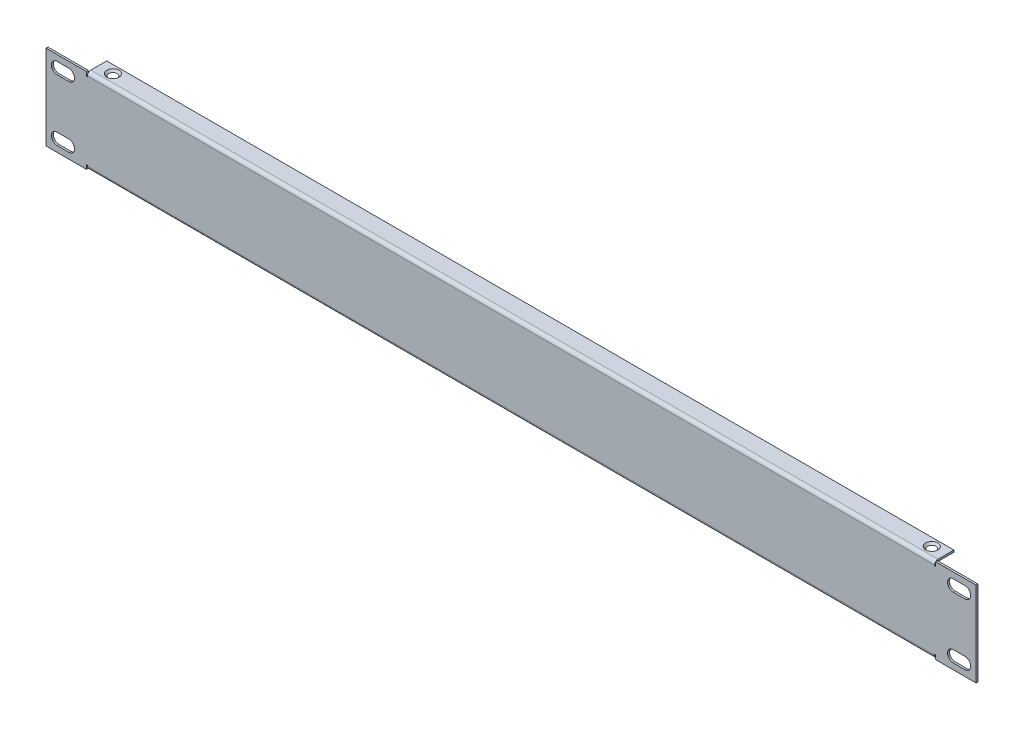
SolidWorks part; units mm, degrees
note: The reader was unsure of these and kept them because the rebuilt part matched: flange length of "Edge-Flange-Mouning".
ref_plane "Front Plane" through (0, 0, 0) normal (0, 0, 1) x (1, 0, 0)
ref_plane "Top Plane" through (0, 0, 0) normal (0, 1, 0) x (1, 0, 0)
ref_plane "Right Plane" through (0, 0, 0) normal (1, 0, 0) x (0, 0, -1)
sketch "Sketch1" plane through (0, 0, 0) normal (0, 0, 1) x (1, 0, 0)
  line L1 (0, 0) -> (-241.3, 0)
  line L2 (0, 0) -> (0, 22)
  line L3 (0, 22) -> (-241.3, 22)
  line L4 (-241.3, 0) -> (-241.3, 22)
  dimension "D1" = 22
  dimension "D2" = 241.3
sheet metal parameters "Sheet-Metal" thickness 1 parameters "D1"=0.7366
base flange "Base-Flange" sketch "Sketch1" thickness 1 reverse thickness direction no parameters "D1"=0.7366
edge flange "Edge-Flange-Mouning" sketch "Sketch12" flange angle 90 flange length 10 flange position material inside bend radius 0.7366 thickness 1 parameters "D6"=10
sketch "Sketch12" plane through (0, 22, -1) normal (0, 1, 0) x (1, 0, 0)
  line L0 (0, 0) -> (-241.3, 0) construction
  line L1 (0, 0) -> (-219.8, 0)
  line L2 (-219.8, 0) -> (-219.8, 9)
  line L3 (-219.8, 9) -> (0, 9)
  line L4 (0, 9) -> (0, 0)
  line L6 (-241.3, 0) -> (-241.3, -1) construction
  dimension "D1" = 21.5
bend "EdgeBend1" bend radius 0.7366 bend angle 90 parameters "D5"=1
sketch "Sketch13" plane through (0, 0, 0) normal (0, 0, 1) x (1, 0, 0)
  line L0 (-241.3, 0) -> (0, 0) construction
  line L2 (0, 0) -> (0, 20.2634) construction
  line L5 (-229.5, 15.9) -> (-235.5, 15.9) construction
  line L6 (-229.5, 12.9) -> (-235.5, 12.9)
  line L7 (-229.5, 18.9) -> (-235.5, 18.9)
  arc A2 (-229.5, 12.9) -> (-229.5, 18.9) centre (-229.5, 15.9) ccw
  arc A3 (-235.5, 18.9) -> (-235.5, 12.9) centre (-235.5, 15.9) ccw
  point P0 (-232.5, 15.9)
  point P13 (-232.5, 15.9)
  dimension "D3" = 232.5
  dimension "D1" = 15.9
extrude "Cut-Extrude-Mounting" cut sketch "Sketch13" against normal blind 1
mirror "Mirror-Vertical" about plane through (0, 0, -1) normal (1, 0, 0) of bodies 103 104
mirror "Mirror-Horizontal"
bend "MirrorBend1" bend radius 0.7366 bend angle 90 parameters "D5"=2
hole_wizard "CSK for M3 Countersunk Flat Head Screw5" positions "Sketch14" profile "Sketch15" countersink size "M3" standard "ISO" end condition through all
sketch "Sketch14" plane through (0, 22, 0) normal (0, 1, 0) x (1, 0, 0)
  line L3 (-219.0634, 10) -> (-205.8, 10) construction
  line L8 (0, 0) -> (0, 10) construction
  point P20 (-212.4317, 5.8683)
  point P30 (212.4317, 5.8683)
sketch "Sketch15" plane through (-212.4317, 22, -5.8683) normal (1, 0, 0) x (0, 0, 1)
  line L0 (0, 0) -> (0, 44)
  line L1 (0, 44) -> (1.6, 44)
  line L2 (1.6, 44) -> (1.6, 1.55)
  line L3 (1.6, 1.55) -> (3.15, 0)
  line L5 (3.15, 0) -> (0, 0)
  line L6 (-1.6, 1.55) -> (-3.15, 0) construction
  line L11 (0, -6.35) -> (0, 107.95) construction
  dimension "Thru Hole Dia." = 3.2
  dimension "Thru Hole Depth" = 44
  dimension "Near C'Sink Dia." = 6.3
  dimension "Near C'Sink Angle" = 90
hole_wizard "CSK for M3 Countersunk Flat Head Screw6" positions "Sketch16" profile "Sketch17" countersink size "M3" standard "ISO" end condition through all
sketch "Sketch16" plane through (0, -22, 0) normal (0, -1, 0) x (-1, 0, 0)
  point P3 (-212.4317, 5.8683)
  point P5 (212.4317, 5.8683)
sketch "Sketch17" plane through (212.4317, -22, -5.8683) normal (1, 0, 0) x (0, 0, -1)
  line L0 (0, 0) -> (0, 44)
  line L1 (0, 44) -> (1.6, 44)
  line L2 (1.6, 44) -> (1.6, 1.55)
  line L3 (1.6, 1.55) -> (3.15, 0)
  line L4 (3.15, 0) -> (0, 0)
  line L5 (-1.6, 1.55) -> (-3.15, 0) construction
  line L6 (0, -6.35) -> (0, 107.95) construction
  dimension "Thru Hole Dia." = 3.2
  dimension "Thru Hole Depth" = 44
  dimension "Near C'Sink Dia." = 6.3
  dimension "Near C'Sink Angle" = 90
flat pattern "Flat-Pattern1" [suppressed]
sketch "Bend-Lines1" plane through (0, 0, 0) normal (0, 0, 1) x (1, 0, 0)
  line L0 (-219.8, -20.3237) -> (219.8, -20.3237) construction
  line L1 (219.8, 20.3237) -> (-219.8, 20.3237) construction
  line L2 (-219.8, -20.3237) -> (219.8, -20.3237) construction
  line L3 (219.8, 20.3237) -> (-219.8, 20.3237) construction
sketch3d "Bounding-Box1" [suppressed]
  line L0 (-241.3, -28.6473, 0) -> (241.3, -28.6473, 0) construction
  line L1 (-241.3, 28.6473, 0) -> (241.3, 28.6473, 0) construction
  line L2 (-241.3, -28.6473, 0) -> (-241.3, 28.6473, 0) construction
  line L3 (241.3, -28.6473, 0) -> (241.3, 28.6473, 0) construction
bend of the flat pattern "Flatten-<EdgeBend1>1"
bend of the flat pattern "Flatten-<MirrorBend1>1"
equation "\"RackUnitHeight\"= 44"
equation "\"RackUnitWidth\"= 482.6"
equation "\"RackUnitInnerWidth\"= 440"
equation "\"RackUnitMountingHoleHorizontalSpacing\"= 465"
equation "\"RackUnitMountingHoleVerticalSpacing\"= 15.9"
equation "\"D1@Sketch1\" = \"RackUnitHeight@Rack unit<1>.Assembly\" / 2"
equation "\"D2@Sketch1\" = \"RackUnitWidth@Rack unit<1>.Assembly\" / 2"
equation "\"D1@Sketch13\" = \"RackUnitMountingHoleVerticalSpacing@Rack unit<1>.Assembly\""
equation "\"D2@Sketch13\" = \"RackUnitMountingHoleHorizontalSpacing\" / 2"
equation "\"D3@Sketch13\" = \"RackUnitMountingHoleHorizontalSpacing@Rack unit<1>.Assembly\" / 2"
